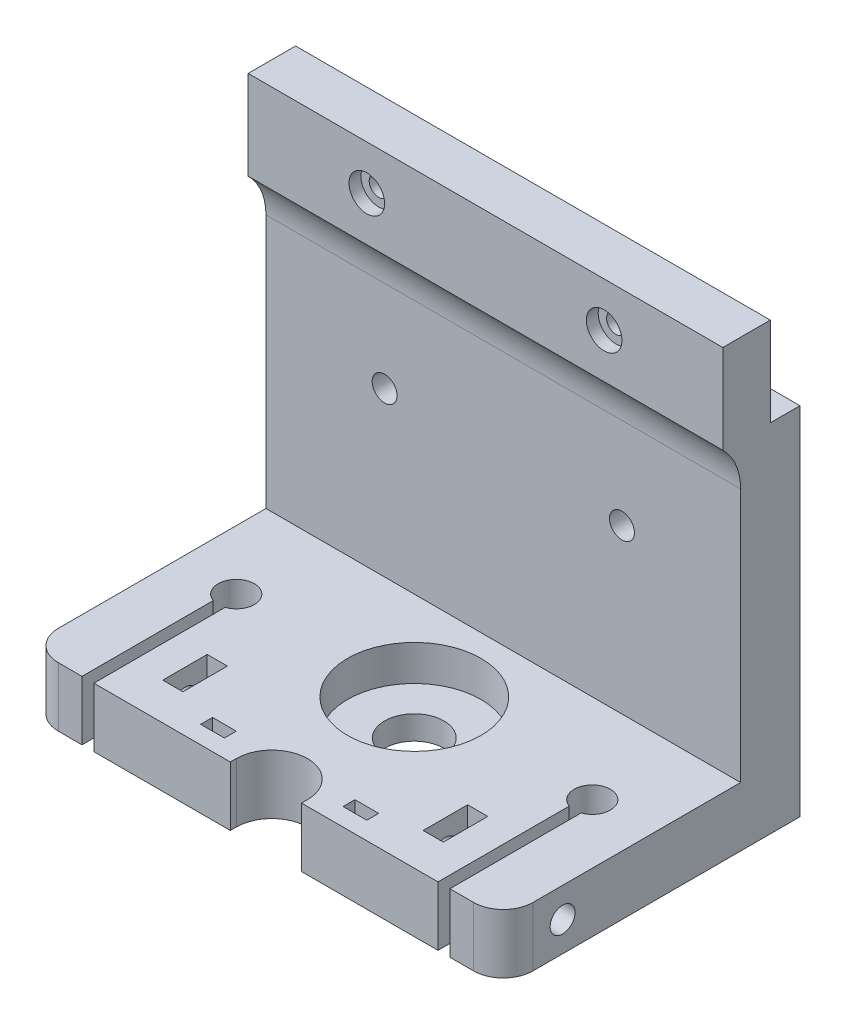
SolidWorks part; units mm, degrees
ref_plane "前基準面" through (0, 0, 0) normal (0, 0, 1) x (1, 0, 0)
ref_plane "上基準面" through (0, 0, 0) normal (0, 1, 0) x (1, 0, 0)
ref_plane "右基準面" through (0, 0, 0) normal (1, 0, 0) x (0, 0, -1)
sketch "草圖1" plane through (0, 0, 0) normal (0, 0, 1) x (1, 0, 0)
  line L1 (-40, 75) -> (40, 75)
  line L2 (-40, 75) -> (-40, -75)
  line L3 (-40, -75) -> (40, -75)
  line L4 (40, 75) -> (40, -75)
  line L5 (-40, 75) -> (40, -75) construction
  line L6 (-40, -75) -> (40, 75) construction
  point P0 (0, 0)
  dimension "D1" = 150
  dimension "D2" = 80
extrude "填料-伸長1" add sketch "草圖1" along normal blind 10
sketch "草圖4" plane through (0, -75, 0) normal (0, -1, 0) x (1, 0, 0)
  line L0 (0, 0) -> (0, 37.8464) construction
  line L1 (-40, 10) -> (40, 10)
  line L2 (-40, 10) -> (-40, 50)
  line L3 (-40, 50) -> (-31, 50)
  line L4 (40, 10) -> (40, 50)
  line L5 (-29, 50) -> (-6, 50)
  line L7 (-31, 50) -> (-31, 27.8814)
  line L9 (-29, 50) -> (-29, 27.8814)
  line L10 (29, 50) -> (29, 27.8814)
  line L11 (31, 50) -> (31, 27.8814)
  line L12 (31, 50) -> (40, 50)
  line L13 (-30, 25) -> (30, 25) construction
  line L14 (-6, 49) -> (-6, 50)
  line L16 (6, 49) -> (6, 50)
  line L17 (6, 50) -> (29, 50)
  arc A0 (-31, 27.8814) -> (-29, 27.8814) centre (-30, 25) ccw
  arc A1 (29, 27.8814) -> (31, 27.8814) centre (30, 25) ccw
  circle A2 centre (0, 25) radius 11.25
  circle A3 centre (0, 25) radius 5
  arc A4 (-6, 49) -> (6, 49) centre (0, 49) ccw
  point P13 (-30, 50)
  line M18 (40, 10) -> (-40, 10)
  dimension "D2" = 6.1
  dimension "D5" = 22.5
  dimension "D6" = 10
  dimension "D7" = 12
  dimension "D1" = 40
  dimension "D3" = 15
  dimension "D4" = 10
  dimension "D8" = 1
  dimension "D9" = 60
extrude "填料-伸長3" add sketch "草圖4" against normal blind 10 contours A4 L14 L5 L9 A0 L7 L3 L2 L4 L12 L11 A1 L10 L17 L16 A2 M18 region at (-39.1056, -75, 30)
sketch "草圖5" plane through (0, -75, 0) normal (0, -1, 0) x (1, 0, 0)
  circle A0 centre (0, 25) radius 11.25
  circle A1 centre (0, 25) radius 5
  dimension "D1" = 10
  dimension "D2" = 22.5
extrude "填料-伸長4" add sketch "草圖5" against normal blind 4
sketch "草圖6" plane through (40, 0, 0) normal (1, 0, 0) x (0, 0, -1)
  line L0 (-50, -65) -> (-50, -75) construction
  circle A0 centre (-40, -70) radius 2.1
  dimension "D2" = 4.2
  dimension "D1" = 10
extrude "除料-伸長1" cut sketch "草圖6" against normal blind 24
sketch "草圖7" plane through (0, -75, 0) normal (0, -1, 0) x (1, 0, 0)
  line L0 (16, 40) -> (21.9431, 40) construction
  line L1 (16, 37.9) -> (16, 42.1) construction
  line L2 (21.9431, 40) -> (0, 24.9665) construction
  line L3 (0, 24.9665) -> (0, 53.0789) construction
  line L4 (-20.2431, 36.25) -> (-20.2431, 43.75)
  line L5 (20.2431, 36.25) -> (23.6431, 36.25)
  line L6 (20.2431, 36.25) -> (20.2431, 43.75)
  line L7 (20.2431, 43.75) -> (23.6431, 43.75)
  line L8 (23.6431, 36.25) -> (23.6431, 43.75)
  line L9 (20.2431, 36.25) -> (23.6431, 43.75) construction
  line L10 (20.2431, 43.75) -> (23.6431, 36.25) construction
  line L11 (-20.2431, 36.25) -> (-23.6431, 36.25)
  line L12 (-23.6431, 36.25) -> (-23.6431, 43.75)
  line L13 (-20.2431, 43.75) -> (-23.6431, 43.75)
  dimension "D1" = 3.4
  dimension "D2" = 7.5
extrude "除料-伸長2" cut sketch "草圖7" against normal blind 24
sketch "草圖8" plane through (-40, 0, 0) normal (-1, 0, 0) x (0, 0, 1)
  circle A0 centre (40, -70) radius 2.1
extrude "除料-伸長3" cut sketch "草圖8" against normal blind 24
sketch "草圖9" plane through (0, 75, 0) normal (0, 1, 0) x (1, 0, 0)
  line L0 (0, 0) -> (0, -54.0504) construction
  line L1 (-40, -10) -> (40, -10)
  line L2 (-40, -10) -> (-40, -50)
  line L3 (-40, -50) -> (40, -50)
  line L4 (40, -10) -> (40, -50)
  line L6 (-21.9203, -25) -> (0, -46.9203) construction
  line L7 (-21.9203, -25) -> (0, -3.0797) construction
  line L8 (0, -3.0797) -> (21.9203, -25) construction
  line L9 (0, -46.9203) -> (21.9203, -25) construction
  line L10 (-21.9203, -25) -> (21.9203, -25) construction
  line L11 (0, -3.0797) -> (0, -46.9203) construction
  circle A0 centre (0, -25) radius 5 construction
  circle A1 centre (0, -25) radius 5 construction
  circle A2 centre (0, -25) radius 11
  circle A3 centre (-21.9203, -25) radius 1.6
  circle A4 centre (0, -46.9203) radius 1.6
  circle A5 centre (21.9203, -25) radius 1.6
  dimension "D1" = 22
  dimension "D3" = 3.2
  dimension "D2" = 31
extrude "填料-伸長5" add sketch "草圖9" against normal blind 10 contours L2 L1 L4 L3 | A2 | A3 | A5 | A4
fillet "圓角1" radius 5 4 edges at (-40, -70, 50) (-40, 70, 50) (40, -70, 50) (40, 70, 50)
sketch "草圖10" plane through (0, 75, 0) normal (0, 1, 0) x (1, 0, 0)
  line L0 (-35, -50) -> (35, -50) construction
  line L1 (-30.9921, -72.1172) -> (-29, -72.1172)
  line L2 (-30.9921, -72.1172) -> (-30.9921, -27.8841)
  line L4 (-29, -72.1172) -> (-29, -27.8814)
  line L5 (-30.9921, -72.1172) -> (-29, -27.8814) construction
  line L6 (-30.9921, -27.8841) -> (-29, -72.1172) construction
  line L8 (29.0016, -72.1183) -> (31, -72.1183)
  line L9 (29.0016, -72.1183) -> (29.0016, -27.882)
  line L11 (31, -72.1183) -> (31, -27.8814)
  line L12 (29.0016, -72.1183) -> (31, -27.8814) construction
  line L13 (29.0016, -27.882) -> (31, -72.1183) construction
  line L14 (-23.6431, -36.25) -> (-20.2431, -36.25)
  line L15 (-23.6431, -36.25) -> (-23.6431, -43.75)
  line L16 (-23.6431, -43.75) -> (-20.2431, -43.75)
  line L17 (-20.2431, -36.25) -> (-20.2431, -43.75)
  line L18 (20.2431, -36.25) -> (23.6431, -36.25)
  line L19 (20.2431, -36.25) -> (20.2431, -43.75)
  line L20 (20.2431, -43.75) -> (23.6431, -43.75)
  line L21 (23.6431, -36.25) -> (23.6431, -43.75)
  arc A0 (-29, -27.8814) -> (-30.9921, -27.8841) centre (-30, -25) ccw
  arc A1 (31, -27.8814) -> (29.0016, -27.882) centre (30, -25) ccw
  point P6 (-29.9961, -50)
  point P14 (30.0008, -50)
extrude "除料-伸長5" cut sketch "草圖10" against normal blind 10 contours L2 A0 L4 L1 | L15 L14 L17 L16 | L19 L18 L21 L20 | L9 A1 L11 L8
sketch "草圖11" plane through (40, 0, 0) normal (1, 0, 0) x (0, 0, -1)
  line L0 (-40, -70) -> (-40, 84.814) construction
  circle A0 centre (-40, 70) radius 2.1
  dimension "D1" = 4.2
extrude "除料-伸長6" cut sketch "草圖11" against normal blind 24
sketch "草圖12" plane through (-40, 0, 0) normal (-1, 0, 0) x (0, 0, 1)
  circle A0 centre (40, 70) radius 2.1
extrude "除料-伸長7" cut sketch "草圖12" against normal blind 24
sketch "草圖14" plane through (0, -75, 0) normal (0, -1, 0) x (1, 0, 0)
  line L0 (0, 49) -> (0, 57.7275) construction
  line L1 (-12, 53.5876) -> (-12, 37.2144) construction
  line L2 (-29, 50) -> (-6, 50) construction
  line L3 (-14, 45) -> (-10, 45)
  line L4 (-14, 45) -> (-14, 47)
  line L5 (-14, 47) -> (-10, 47)
  line L6 (-10, 45) -> (-10, 47)
  line L7 (-14, 45) -> (-10, 47) construction
  line L8 (-14, 47) -> (-10, 45) construction
  line L9 (14, 45) -> (10, 45)
  line L10 (10, 45) -> (10, 47)
  line L11 (14, 47) -> (10, 47)
  line L12 (14, 45) -> (14, 47)
  point P6 (-12, 46)
  dimension "D1" = 4
  dimension "D2" = 2
  dimension "D3" = 12
  dimension "D4" = 4
extrude "除料-伸長9" cut sketch "草圖14" against normal blind 10
sketch "草圖16" plane through (0, 0, 10) normal (0, 0, 1) x (1, 0, 0)
  line L1 (-20, -37.5) -> (20, -37.5) construction
  line L2 (-20, -37.5) -> (-20, 37.5) construction
  line L3 (-20, 37.5) -> (20, 37.5) construction
  line L4 (20, -37.5) -> (20, 37.5) construction
  line L5 (-20, -37.5) -> (20, 37.5) construction
  line L6 (-20, 37.5) -> (20, -37.5) construction
  circle A0 centre (-20, 37.5) radius 2.1
  circle A1 centre (20, 37.5) radius 2.1
  circle A2 centre (20, -37.5) radius 2.1
  circle A3 centre (-20, -37.5) radius 2.1
  point P0 (0, 0)
  dimension "D3" = 4.2
  dimension "D1" = 40
  dimension "D2" = 75
extrude "除料-伸長10" cut sketch "草圖16" against normal through all
sketch "草圖17" plane through (40, 0, 0) normal (1, 0, 0) x (0, 0, -1)
  line L0 (-10, -65) -> (-10, 65) construction
  line L1 (-10, -15) -> (-13, -15) construction
  line L2 (-13, -15) -> (-13, 0) construction
  line L3 (-13, 0) -> (-5, 0) construction
  line L4 (-5, 0) -> (-5, -15)
  line L5 (-5, -15) -> (0, -15)
  line L6 (0, -75) -> (0, 75) construction
  line L7 (-10, -65) -> (-45, -65) construction
  line L8 (-5, 0) -> (-10, 0)
  line L9 (-10, 0) -> (-10, 65)
  line L10 (-10, 65) -> (-50, 65)
  line L11 (-50, 65) -> (-50, 75)
  line L12 (-50, 75) -> (0, 75)
  line L13 (0, 75) -> (0, -15)
  dimension "D1" = 50
  dimension "D2" = 15
  dimension "D3" = 8
  dimension "D4" = 3
extrude "除料-伸長11" cut sketch "草圖17" against normal through all
sketch "草圖18" plane through (40, 0, 0) normal (1, 0, 0) x (0, 0, -1)
  line L0 (-10, -15) -> (-13, -15)
  line L1 (-10, -65) -> (-10, 0) construction
  line L2 (-13, -15) -> (-13, 0)
  line L3 (-13, 0) -> (-10, 0)
  line L4 (-10, -15) -> (-10, 0)
  dimension "D1" = 3
extrude "填料-伸長7" add sketch "草圖18" along direction (1, 0, 0) on the side against the normal blind 80
fillet "圓角2" radius 10 1 edges at (0, -15, 10)
sketch "草圖19" plane through (0, 0, 13) normal (0, 0, 1) x (1, 0, 0)
  line L0 (-40, -7.5) -> (40, -7.5) construction
  line L1 (-40, 0) -> (-40, -15) construction
  line L2 (40, 0) -> (40, -15) construction
  line L3 (40, -7.5) -> (0, 0) construction
  line L4 (0, 0) -> (0, -15) construction
  line L5 (-40, -15) -> (40, -15) construction
  circle A0 centre (-20, -7.5) radius 1.6
  circle A1 centre (20, -7.5) radius 1.6
  dimension "D2" = 3.2
  dimension "D1" = 20
extrude "除料-伸長12" cut sketch "草圖19" against normal blind 80
sketch "草圖20" plane through (0, 0, 13) normal (0, 0, 1) x (1, 0, 0)
  circle A0 centre (-20, -7.5) radius 3
  circle A1 centre (20, -7.5) radius 3
  dimension "D1" = 6
  dimension "D2" = 6
extrude "除料-伸長13" cut sketch "草圖20" against normal blind 2
